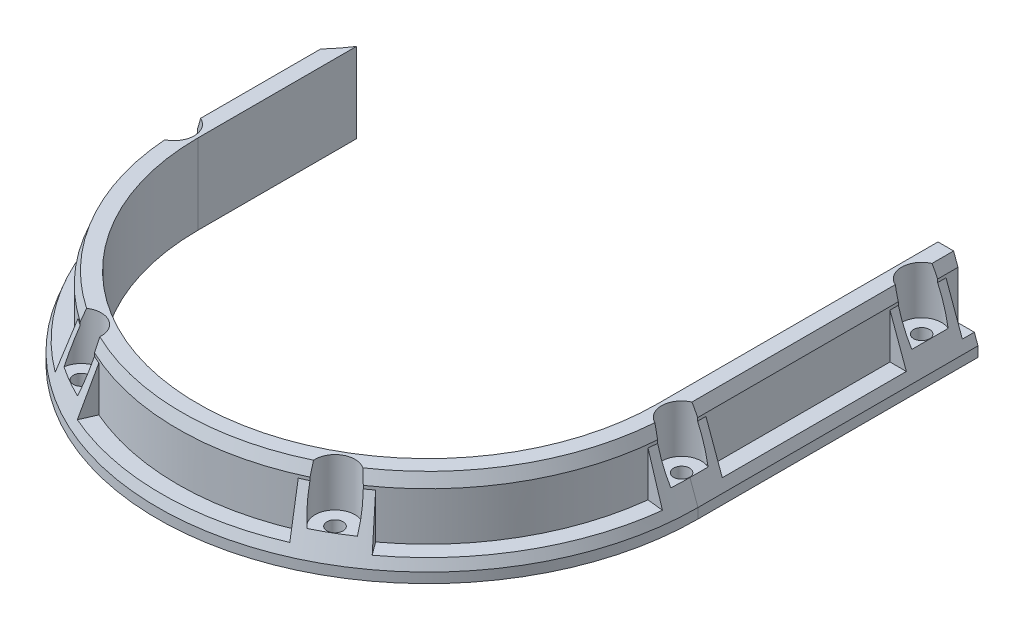
SolidWorks part; units mm, degrees
ref_plane "Front Plane" through (0, 0, 0) normal (0, 0, 1) x (1, 0, 0)
ref_plane "Top Plane" through (0, 0, 0) normal (0, 1, 0) x (1, 0, 0)
ref_plane "Right Plane" through (0, 0, 0) normal (1, 0, 0) x (0, 0, -1)
sketch "Sketch1" plane through (0, 0, 0) normal (0, 1, 0) x (1, 0, 0)
  line L1 (0, 0) -> (40.005, 0) construction
  line L2 (113.03, 0) -> (113.03, -76.2) construction
  line L4 (40.005, -76.2) -> (40.005, -25.8407)
  line L5 (186.055, -76.2) -> (186.055, 0)
  line L6 (186.055, 0) -> (182.88, 0) construction
  line L7 (47.625, 0) -> (186.055, 0) construction
  line L8 (47.625, 0) -> (182.88, 0) construction
  line L10 (186.055, 0) -> (47.625, 0) construction
  line L11 (186.055, 0) -> (186.055, 12.7)
  line L12 (186.055, 12.7) -> (47.625, 12.7)
  line L13 (47.625, 0) -> (47.625, 12.7)
  arc A0 (40.005, -76.2) -> (186.055, -76.2) centre (113.03, -76.2) ccw
  arc A1 (40.005, -25.8407) -> (47.625, 0) centre (0, 0) ccw
  dimension "D2" = 146.05
  dimension "D3" = 95.25
  dimension "D1" = 76.2
  dimension "D4" = 12.7
sketch "Sketch2" plane through (0, 0, 0) normal (0, 1, 0) x (1, 0, 0)
  line L0 (186.055, -76.2) -> (186.055, 0) construction
  line L1 (186.055, 0) -> (186.055, 12.7) construction
  line L2 (27.305, -76.2) -> (33.655, -76.2) construction
  line L4 (40.005, -76.2) -> (40.005, -25.8407) construction
  line L5 (186.055, -76.2) -> (186.055, 0)
  line L6 (186.055, 0) -> (186.055, 12.7)
  line L9 (40.005, -76.2) -> (40.005, -25.8407)
  line L10 (186.055, 12.7) -> (192.405, 12.7)
  line L11 (192.405, 12.7) -> (192.405, -76.2)
  line L12 (33.655, -33.6969) -> (33.655, -76.2)
  line L13 (33.655, -76.2) -> (40.005, -76.2) construction
  line L14 (27.305, -39.0202) -> (27.305, -76.2)
  line L15 (192.405, 12.7) -> (198.755, 12.7)
  line L16 (198.755, 12.7) -> (198.755, -76.2)
  arc A0 (40.005, -76.2) -> (186.055, -76.2) centre (113.03, -76.2) ccw construction
  arc A1 (27.305, -39.0202) -> (40.005, -25.8407) centre (0, 0) ccw
  arc A2 (40.005, -76.2) -> (186.055, -76.2) centre (113.03, -76.2) ccw
  arc A4 (33.655, -33.6969) -> (40.005, -25.8407) centre (0, 0) ccw
  arc A5 (33.655, -76.2) -> (192.405, -76.2) centre (113.03, -76.2) ccw
  arc A6 (27.305, -76.2) -> (198.755, -76.2) centre (113.03, -76.2) ccw
  point P18 (0, 0)
  dimension "D1" = 6.35
  dimension "D2" = 6.35
  dimension "D3" = 6.35
  dimension "D4" = 6.35
extrude "Boss-Extrude1" add sketch "Sketch2" along normal blind 25.4 contours L12 A5 L11 L10 L6 L5 A2 L9 A1 region at (188.3684, 0, 38.1)
extrude "Boss-Extrude2" add sketch "Sketch2<3>" along normal blind 6.35 contours L14 A6 L16 L15 L11 A5 L12 A1 region at (195.58, 0, -10.2528)
sketch "Sketch2<3>" plane through (0, 0, 0) normal (0, 1, 0) x (1, 0, 0) same geometry as "Sketch2"
chamfer "Chamfer1" distance 3.175 angle 20 3 edges at (27.305, 6.35, 57.6101) (198.755, 6.35, 31.75) (113.03, 6.35, 161.925) first distance on face at (27.305, 3.175, 57.6101) first distance on face at (198.755, 3.175, 31.75) first distance on face at (113.03, 3.175, 119.0625)
sketch3d "3DSketch1"
  line L0 (28.4606, 6.35, 76.2) -> (33.655, 25.4, 76.2)
ref_plane "Plane1" through (0, 0, 76.2) normal (0, 0, 1) x (1, 0, 0)
sketch "Sketch4" plane through (0, 0, 76.2) normal (0, 0, 1) x (1, 0, 0)
  line L0 (28.4606, 6.35) -> (33.655, 20.6215)
  line L1 (33.655, 25.4) -> (33.655, 6.35) construction
  line L2 (27.305, 3.175) -> (28.4606, 6.35) construction
  line L3 (113.03, 0) -> (113.03, 25.86) construction
  line L4 (33.655, 20.6215) -> (33.655, 6.35)
  line L5 (33.655, 6.35) -> (28.4606, 6.35)
extrude "Boss-Extrude3" add sketch "Sketch4" against normal blind 8.89 separate body contours L5 L0 L4
revolve "Revolve1" add sketch "Sketch4<4>" angle 6.5 about L3
sketch "Sketch4<4>" plane through (0, 0, 76.2) normal (0, 0, 1) x (1, 0, 0) same geometry as "Sketch4"
chamfer "Chamfer2" distance 3.81 angle 20 3 edges at (33.655, 25.4, 54.9485) (192.405, 25.4, 31.75) (113.03, 25.4, 155.575) first distance on face at (33.655, 15.875, 54.9485) first distance on face at (192.405, 15.875, 31.75) first distance on face at (113.03, 15.875, 115.8875)
ref_plane "Plane2" through (113.03, 0, 0) normal (-1, 0, 0) x (0, 0, 1)
mirror "Mirror1" about plane through (113.03, 0, 0) normal (-1, 0, 0) of bodies 104 103
pattern_circular "CirPattern1" count 3 over 120 about axis through (113.03, 0, 76.2) along (0, 1, 0) of bodies 104
mirror "Mirror2" about plane through (56.515, 0, 174.0869) normal (0.866, 0, 0.5) of bodies 107
mirror "Mirror3" about plane through (169.545, 0, 174.0869) normal (0.866, 0, -0.5) of bodies 108
sketch "Sketch6" plane through (0, 0, 0) normal (0, 1, 0) x (1, 0, 0)
  line L0 (73.3425, -144.9408) -> (113.03, -76.2) construction
  line L1 (113.03, -76.2) -> (152.7175, -144.9408) construction
  line L2 (152.7175, -144.9408) -> (155.3147, -149.4392) construction
  line L3 (113.03, -76.2) -> (113.03, -165.762) construction
  arc A0 (33.655, -76.2) -> (192.405, -76.2) centre (113.03, -76.2) ccw construction
pattern_linear "LPattern1" count 2 spacing 76.2 along (0, 0, -1) of bodies 106
mirror "Mirror4" about plane through (226.06, 0, 0) normal (0, 0, -1) of bodies 114
combine bodies "Combine2" operation type add bodies to combine 105 109 115 106 107 108 102 110 103 114 104
sketch "Sketch8" plane through (0, 25.4, 0) normal (0, 1, 0) x (1, 0, 0)
  line L0 (27.305, -76.2) -> (37.6985, -76.2)
  circle A0 centre (32.5017, -76.2) radius 2.54
  arc A2 (35.0417, -76.2) -> (191.0183, -76.2) centre (113.03, -76.2) ccw construction
  circle A3 centre (72.7659, -145.9395) radius 2.54
  circle A4 centre (153.2941, -145.9395) radius 2.54
  circle A5 centre (193.5583, -76.2) radius 2.54
  circle A6 centre (32.5017, -76.2) radius 6.35
  circle A7 centre (72.7659, -145.9395) radius 6.35
  circle A8 centre (153.2941, -145.9395) radius 6.35
  circle A9 centre (193.5583, -76.2) radius 6.35
  circle A10 centre (193.5583, 0) radius 2.54
  circle A11 centre (193.5583, 0) radius 6.35
  dimension "D1" = 5.08
  dimension "D4" = 12.7
  dimension "D5" = 2
  dimension "D2" = 4
  dimension "D3" = 4
extrude "Cut-Extrude1" cut sketch "Sketch8" against normal through all both and the other way through all contours A0 | A3 | A4 | A5 | A10
extrude "Cut-Extrude2" cut sketch "Sketch8<3>" against normal blind 15.24 contours A6 | A7 | A8 | A9 | A11
sketch "Sketch8<3>" plane through (0, 25.4, 0) normal (0, 1, 0) x (1, 0, 0) same geometry as "Sketch8"
